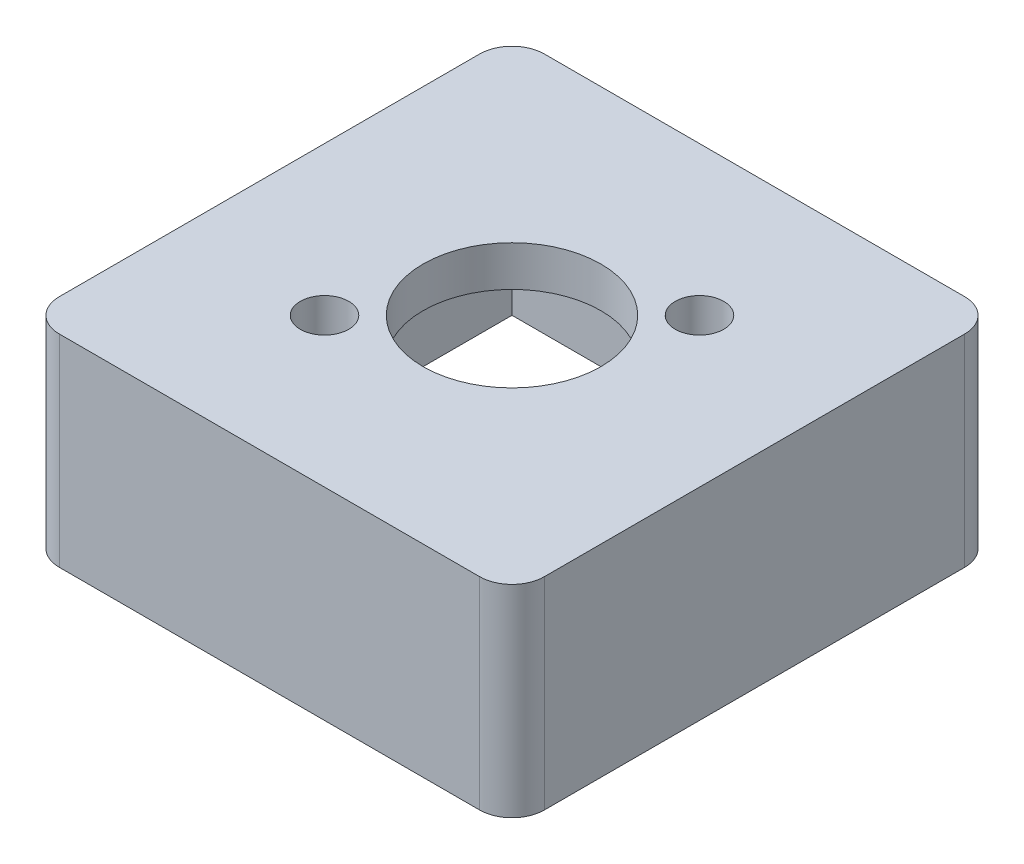
SolidWorks part; units mm, degrees
ref_plane "Front Plane" through (0, 0, 0) normal (0, 0, 1) x (1, 0, 0)
ref_plane "Top Plane" through (0, 0, 0) normal (0, 1, 0) x (1, 0, 0)
ref_plane "Right Plane" through (0, 0, 0) normal (1, 0, 0) x (0, 0, -1)
sketch "Sketch1" plane through (0, 0, 0) normal (0, 1, 0) x (1, 0, 0)
  line L1 (-19.05, -19.05) -> (19.05, -19.05)
  line L2 (-19.05, -19.05) -> (-19.05, 19.05)
  line L3 (-19.05, 19.05) -> (19.05, 19.05)
  line L4 (19.05, -19.05) -> (19.05, 19.05)
  line L5 (-19.05, -19.05) -> (19.05, 19.05) construction
  line L6 (-19.05, 19.05) -> (19.05, -19.05) construction
  line L7 (-15.875, -15.875) -> (15.875, -15.875)
  line L8 (-15.875, -15.875) -> (-15.875, 15.875)
  line L9 (-15.875, 15.875) -> (15.875, 15.875)
  line L10 (15.875, -15.875) -> (15.875, 15.875)
  line L11 (-15.875, -15.875) -> (15.875, 15.875) construction
  line L12 (-15.875, 15.875) -> (15.875, -15.875) construction
  circle A0 centre (-7.3638, -7.3638) radius 1.905
  circle A1 centre (7.3638, 7.3638) radius 1.905
  circle A2 centre (0, 0) radius 6.985
  point P0 (0, 0)
  point P6 (0, 0)
  dimension "D2" = 3.81
  dimension "D5" = 13.97
  dimension "D1" = 20.828
  dimension "D3" = 38.1
  dimension "D4" = 3.175
extrude "Boss-Extrude1" add sketch "Sketch1" along normal blind 3.175 contours L7 L10 L9 L8 A0 A1 | L1 L4 L3 L2 L10 L7 L8 L9 region at (-18.5112, 0, 0) region at (-15.426, 0, 0)
extrude "Boss-Extrude2" add sketch "Sketch1<3>" against normal blind 12.7 contours L1 L4 L3 L2 L10 L7 L8 L9 region at (-18.5112, 0, 0)
sketch "Sketch1<3>" plane through (0, 0, 0) normal (0, 1, 0) x (1, 0, 0) same geometry as "Sketch1"
fillet "Fillet1" radius 2.54 4 edges at (-19.05, -4.7625, -19.05) (19.05, -4.7625, -19.05) (-19.05, -4.7625, 19.05) (19.05, -4.7625, 19.05)
